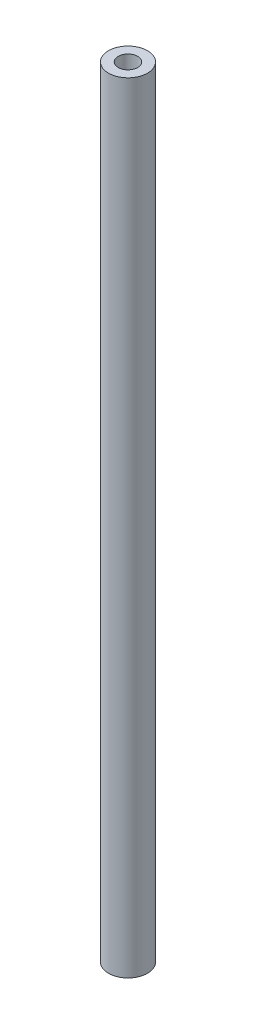
SolidWorks part; units mm, degrees
ref_plane "Front Plane" through (0, 0, 0) normal (0, 0, 1) x (1, 0, 0)
ref_plane "Top Plane" through (0, 0, 0) normal (0, 1, 0) x (1, 0, 0)
ref_plane "Right Plane" through (0, 0, 0) normal (1, 0, 0) x (0, 0, -1)
sketch "Sketch1" plane through (0, 0, 0) normal (0, 1, 0) x (1, 0, 0)
  circle A0 centre (0, 0) radius 6.35
  circle A1 centre (0, 0) radius 3.175
  dimension "D1" = 12.7
  dimension "D2" = 3.175
extrude "Boss-Extrude1" add sketch "Sketch1" along normal blind 254
equation "\"Pstrut_L\"= 36in"
equation "\"Pstrut_D\"= 1in"
equation "\"Pstrut_T\"= 0.25"
equation "\"Sstrut_L\"= 36in"
equation "\"Sstrut_D\"= 0.5in"
equation "\"Sstrut_T\"= 0.125"
equation "\"Dstrut_L\"= 10in"
equation "\"Dstrut_D\"= 0.5in"
equation "\"Dstrut_T\"= 0.125"
equation "\"D1@Sketch1\"=\"Dstrut_D\""
equation "\"D2@Sketch1\"=\"Dstrut_T\""
equation "\"D1@Boss-Extrude1\"=\"Dstrut_L\""
